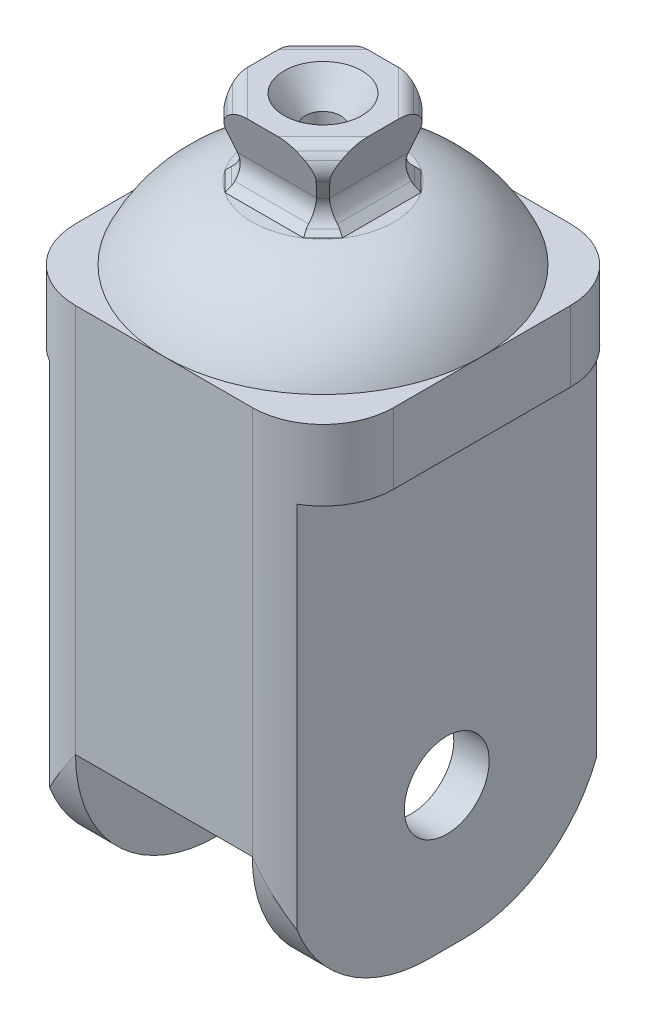
SolidWorks part; units mm, degrees
material "6061-T6 (SS)"
ref_plane "Front Plane" through (0, 0, 0) normal (0, 0, 1) x (1, 0, 0)
ref_plane "Top Plane" through (0, 0, 0) normal (0, 1, 0) x (1, 0, 0)
ref_plane "Right Plane" through (0, 0, 0) normal (1, 0, 0) x (0, 0, -1)
sketch "Sketch4" plane through (0, 0, 0) normal (0, 0, 1) x (1, 0, 0)
  line L1 (-8.5, -5.5) -> (8.5, -5.5)
  line L2 (-8.5, -5.5) -> (-8.5, 5.5)
  line L3 (-8.5, 5.5) -> (8.5, 5.5)
  line L4 (8.5, -5.5) -> (8.5, 5.5)
  line L5 (-8.5, -5.5) -> (8.5, 5.5) construction
  line L6 (-8.5, 5.5) -> (8.5, -5.5) construction
  point P0 (0, 0)
  dimension "D1" = 11
  dimension "D2" = 17
extrude "Boss-Extrude2" add sketch "Sketch4" along normal mid plane 17
sketch "Sketch5" plane through (0, 0, 0) normal (1, 0, 0) x (0, 0, -1)
  line L0 (0, -10) -> (0, 10) construction
  line L1 (8.5, 5.5) -> (6.5025, -1.2915)
  line L2 (8.5, -5.5) -> (7.2593, -4.2593)
  line L3 (-8.5, -5.5) -> (-7.2593, -4.2593)
  line L4 (-8.5, 5.5) -> (-6.5025, -1.2915)
  line L5 (-8.5, 5.5) -> (-8.5, -5.5)
  line L6 (8.5, -5.5) -> (8.5, 5.5)
  arc A0 (7.2593, -4.2593) -> (6.5025, -1.2915) centre (9.3806, -2.138) cw
  arc A1 (-7.2593, -4.2593) -> (-6.5025, -1.2915) centre (-9.3806, -2.138) ccw
  point P12 (6, -3)
  point P16 (-6, -3)
  dimension "D5" = 3
  dimension "D1" = 10
  dimension "D2" = 20
  dimension "D3" = 6
  dimension "D4" = 45
extrude "Cut-Extrude1" cut sketch "Sketch5" against normal mid plane 27
sketch "Sketch7" plane through (0, 0, 0) normal (0, 0, 1) x (1, 0, 0)
  line L0 (0, -10) -> (0, 10) construction
  line L1 (8.5, 5.5) -> (6.5025, -1.2915)
  line L2 (8.5, -5.5) -> (7.2593, -4.2593)
  line L3 (-8.5, -5.5) -> (-7.2593, -4.2593)
  line L4 (-8.5, 5.5) -> (-6.5025, -1.2915)
  line L5 (-8.5, 5.5) -> (-8.5, -5.5)
  line L6 (8.5, -5.5) -> (8.5, 5.5)
  line L7 (8.5, -4.2593) -> (8.5, -5.5) construction
  arc A0 (7.2593, -4.2593) -> (6.5025, -1.2915) centre (9.3806, -2.138) cw
  arc A1 (-7.2593, -4.2593) -> (-6.5025, -1.2915) centre (-9.3806, -2.138) ccw
  point P12 (-6, -3)
  dimension "D3" = 3
  dimension "D1" = 20
  dimension "D2" = 45
  dimension "D4" = 16.389
extrude "Cut-Extrude2" cut sketch "Sketch7" against normal mid plane 27
sketch "Sketch8" plane through (0, 5.5, 0) normal (0, 1, 0) x (1, 0, 0)
  line L0 (3.5355, 3.5355) -> (-3.5355, -3.5355) construction
  line L1 (-5, 0) -> (5, 0) construction
  line L2 (-3.5355, 3.5355) -> (3.5355, -3.5355) construction
  line L3 (0, 5) -> (0, -5) construction
  dimension "D1" = 10
  dimension "D2" = 10
  dimension "D3" = 10
  dimension "D4" = 45
  dimension "D5" = 45
  dimension "D6" = 10
sketch "Sketch9" plane through (0, 0, 0) normal (0, 1, 0) x (1, 0, 0)
  line L0 (3.5355, 3.5355) -> (-3.5355, -3.5355) construction
  line L1 (-5, 0) -> (5, 0) construction
  line L2 (-3.5355, 3.5355) -> (3.5355, -3.5355) construction
  line L3 (0, 5) -> (0, -5) construction
  point P8 (0, 0)
  point P10 (0, 0)
  point P11 (0, 0)
  dimension "D1" = 10
  dimension "D2" = 10
  dimension "D3" = 10
  dimension "D4" = 45
  dimension "D5" = 45
  dimension "D6" = 10
ref_plane "Plane1" through (0, 0, 0) normal (0.7071, 0, 0.7071) x (0.7071, 0, -0.7071)
ref_plane "Plane2" through (0, 0, 0) normal (0.7071, 0, -0.7071) x (-0.7071, 0, -0.7071)
sketch "Sketch11" plane through (0, 0, 0) normal (0.7071, 0, 0.7071) x (0.7071, 0, -0.7071)
  line L0 (-10, 5.5) -> (10, 5.5) construction
  line L1 (0, -5.5) -> (0, 5.5) construction
  line L2 (10, 5.5) -> (10, -5.5) construction
  line L3 (0, -5.5) -> (12.0208, -5.5) construction
  line L4 (10, -5.5) -> (0, -5.5) construction
  line L5 (10, -5.5) -> (9.1595, -4.6595)
  line L6 (10, 5.5) -> (10, 2.3) construction
  line L7 (0, 5.5) -> (8.25, 5.5) construction
  line L8 (9.6935, 1.5413) -> (8.4993, -1.4144)
  line L10 (10, -5.5) -> (14, -5.5)
  line L11 (14, -5.5) -> (14, 5.5)
  line L12 (14, 5.5) -> (8.25, 5.5)
  line L13 (-14, 5.5) -> (-8.25, 5.5)
  line L14 (-9.6935, 1.5413) -> (-8.4993, -1.4144)
  line L15 (-10, -5.5) -> (-9.1595, -4.6595)
  line L16 (-10, -5.5) -> (-14, -5.5)
  line L17 (-14, -5.5) -> (-14, 5.5)
  arc A0 (9.5819, 4.0331) -> (8.25, 5.5) centre (6.1993, 2.3) ccw
  arc A1 (9.5819, 4.0331) -> (9.6935, 1.5413) centre (6.9119, 2.6651) cw
  arc A2 (9.1595, -4.6595) -> (8.4993, -1.4144) centre (11.2808, -2.5382) cw
  arc A3 (-9.5819, 4.0331) -> (-9.6935, 1.5413) centre (-6.9119, 2.6651) ccw
  arc A4 (-9.5819, 4.0331) -> (-8.25, 5.5) centre (-6.1993, 2.3) cw
  arc A5 (-9.1595, -4.6595) -> (-8.4993, -1.4144) centre (-11.2808, -2.5382) ccw
  dimension "D7" = 3
  dimension "D8" = 3
  dimension "D1" = 20
  dimension "D2" = 11
  dimension "D3" = 45
  dimension "D4" = 8.25
  dimension "D5" = 3.2
  dimension "D6" = 22
  dimension "D9" = 4
extrude "Cut-Extrude3" cut sketch "Sketch11" against normal mid plane 27
sketch "Sketch12" plane through (0, 0, 0) normal (0.7071, 0, -0.7071) x (-0.7071, 0, -0.7071)
  line L0 (-10, 5.5) -> (10, 5.5) construction
  line L1 (0, -5.5) -> (0, 5.5) construction
  line L2 (10, 5.5) -> (10, -5.5) construction
  line L3 (10, -5.5) -> (0, -5.5) construction
  line L4 (10, -5.5) -> (9.1595, -4.6595)
  line L5 (10, 5.5) -> (10, 2.3) construction
  line L6 (0, 5.5) -> (8.25, 5.5) construction
  line L7 (9.6935, 1.5413) -> (8.4993, -1.4144)
  line L8 (10, -5.5) -> (14, -5.5)
  line L9 (14, -5.5) -> (14, 5.5)
  line L10 (14, 5.5) -> (8.25, 5.5)
  line L11 (-14, 5.5) -> (-8.25, 5.5)
  line L12 (-9.6935, 1.5413) -> (-8.4993, -1.4144)
  line L13 (-10, -5.5) -> (-9.1595, -4.6595)
  line L14 (-10, -5.5) -> (-14, -5.5)
  line L15 (-14, -5.5) -> (-14, 5.5)
  arc A0 (9.5819, 4.0331) -> (8.25, 5.5) centre (6.1993, 2.3) ccw
  arc A1 (9.5819, 4.0331) -> (9.6935, 1.5413) centre (6.9119, 2.6651) cw
  arc A2 (9.1595, -4.6595) -> (8.4993, -1.4144) centre (11.2808, -2.5382) cw
  arc A3 (-9.5819, 4.0331) -> (-9.6935, 1.5413) centre (-6.9119, 2.6651) ccw
  arc A4 (-9.5819, 4.0331) -> (-8.25, 5.5) centre (-6.1993, 2.3) cw
  arc A5 (-9.1595, -4.6595) -> (-8.4993, -1.4144) centre (-11.2808, -2.5382) ccw
  dimension "D7" = 3
  dimension "D8" = 3
  dimension "D1" = 20
  dimension "D2" = 11
  dimension "D3" = 45
  dimension "D4" = 8.25
  dimension "D5" = 3.2
  dimension "D6" = 22
  dimension "D9" = 4
extrude "Cut-Extrude4" cut sketch "Sketch12" against normal mid plane 27
sketch "Sketch14" plane through (0, 0, 0) normal (0, 0, 1) x (1, 0, 0)
  line L0 (0, 5.5) -> (0, -5.5) construction
  line L1 (0, 5.5) -> (5.5, 5.5)
  line L2 (3.1673, 5.5) -> (8.5, 5.5) construction
  line L3 (5.5, 5.5) -> (5.5, 1.5) construction
  line L4 (0, 1.5) -> (2.5, 1.5) construction
  line L5 (2.5, 1.5) -> (5.5, 5.5)
  line L6 (2.5, 1.5) -> (2.5, -5.5)
  line L7 (-5.6421, -5.5) -> (5.6421, -5.5) construction
  line L8 (0, -5.5) -> (0, 5.5)
  line L9 (2.5, -5.5) -> (0, -5.5)
  dimension "D1" = 11
  dimension "D2" = 5.5
  dimension "D3" = 4
  dimension "D4" = 2.5
revolve "Cut-Revolve1" cut sketch "Sketch14" angle 360 about L8
fillet "Fillet1" radius 2 4 edges at (5.8336, 5.5, -5.8336) (-5.8336, 5.5, -5.8336) (-5.8336, 5.5, 5.8336) (5.8336, 5.5, 5.8336)
sketch "Sketch15" plane through (0, 0, 0) normal (1, 0, 0) x (0, 0, -1)
  line L0 (0, -5.5) -> (0, -15.5) construction
  line L1 (-5.6421, -5.5) -> (5.6421, -5.5) construction
  line L3 (0, -15.5) -> (22.5, -15.5)
  line L4 (0, -15.5) -> (0, -5.5)
  line L5 (0, -5.5) -> (0, -5.3)
  line L6 (0, -5.3) -> (9.998, -5.3)
  arc A0 (9.998, -5.3) -> (22.5, -15.5) centre (6.077, -22.8677) cw
  dimension "D4" = 18
  dimension "D1" = 10
  dimension "D2" = 10
  dimension "D3" = 22.5
  dimension "D5" = 0.2
revolve "Revolve1" add sketch "Sketch15" angle 360 about L0
sketch "Sketch16" plane through (0, -15.5, 0) normal (0, -1, 0) x (1, 0, 0)
  line L1 (-22.5, -22.5) -> (22.5, -22.5)
  line L2 (-22.5, -22.5) -> (-22.5, 22.5)
  line L3 (-22.5, 22.5) -> (22.5, 22.5)
  line L4 (22.5, -22.5) -> (22.5, 22.5)
  line L5 (-22.5, -22.5) -> (22.5, 22.5) construction
  line L6 (-22.5, 22.5) -> (22.5, -22.5) construction
  point P0 (0, 0)
  dimension "D1" = 45
  dimension "D2" = 45
extrude "Boss-Extrude3" add sketch "Sketch16" along normal blind 75
sketch "Sketch17" plane through (0, 0, 22.5) normal (0, 0, 1) x (1, 0, 0)
  line L0 (-22.5, -90.5) -> (-22.5, -15.5) construction
  line L1 (-22.5, -25.5) -> (-17.5, -25.5)
  line L2 (-22.5, -25.5) -> (-22.5, -90.5)
  line L3 (-22.5, -90.5) -> (-17.5, -90.5)
  line L4 (-17.5, -25.5) -> (-17.5, -90.5)
  line L5 (22.5, -90.5) -> (-22.5, -90.5) construction
  line L6 (22.5, -90.5) -> (22.5, -15.5) construction
  line L7 (22.5, -25.5) -> (17.5, -25.5)
  line L8 (22.5, -25.5) -> (22.5, -90.5)
  line L9 (22.5, -90.5) -> (17.5, -90.5)
  line L10 (17.5, -25.5) -> (17.5, -90.5)
  dimension "D1" = 5
  dimension "D2" = 65
  dimension "D3" = 65
  dimension "D4" = 5
extrude "Cut-Extrude5" cut sketch "Sketch17" against normal through all
sketch "Sketch18" plane through (17.5, 0, 0) normal (1, 0, 0) x (0, 0, -1)
  line L0 (-22.5, -25.5) -> (-22.5, -90.5) construction
  line L1 (22.5, -90.5) -> (-22.5, -90.5) construction
  circle A0 centre (0, -70.5) radius 6
  dimension "D2" = 12
  dimension "D1" = 22.5
  dimension "D3" = 20
extrude "Cut-Extrude6" cut sketch "Sketch18" against normal through all
sketch "Sketch19" plane through (0, 0, 0) normal (1, 0, 0) x (0, 0, -1)
  line L0 (-22.5, -90.5) -> (-22.5, -70.5)
  line L1 (-22.5, -25.5) -> (-22.5, -90.5) construction
  line L2 (-22.5, -70.5) -> (-12.5, -70.5)
  line L3 (11.0876, -64.7281) -> (22.5, -58.7872)
  line L5 (22.5, -90.5) -> (-22.5, -90.5)
  line L10 (-4.781, -70.5) -> (4.7661, -70.5) construction
  line L12 (22.5, -25.5) -> (22.5, -90.5) construction
  line L13 (22.5, -58.7872) -> (22.5, -90.5)
  arc A1 (11.0876, -64.7281) -> (-12.5, -70.5) centre (0, -70.5) ccw
  dimension "D2" = 25
  dimension "D1" = 20
  dimension "D3" = 20
  dimension "D4" = 22.5
  dimension "D5" = 27.5
  dimension "D6" = 11.4124
extrude "Cut-Extrude7" cut sketch "Sketch19" against normal mid plane 25
sketch "Sketch20" plane through (0, -90.5, 0) normal (0, -1, 0) x (1, 0, 0)
  line L0 (-22.5, -22.5) -> (-22.5, 22.5) construction
  line L1 (-17.5, 22.5) -> (-22.5, 22.5) construction
  circle A0 centre (-10.5, 10.5) radius 1.5
  dimension "D1" = 3
  dimension "D2" = 12
  dimension "D3" = 12
extrude "Cut-Extrude8" cut sketch "Sketch20" against normal blind 75
fillet "Fillet2" radius 20 4 edges at (-15, -90.5, -22.5) (15, -90.5, -22.5) (-15, -90.5, 22.5) (15, -90.5, 22.5)
fillet "Fillet3" radius 10 4 edges at (22.5, -20.5, 22.5) (-22.5, -20.5, 22.5) (-22.5, -20.5, -22.5) (22.5, -20.5, -22.5)
